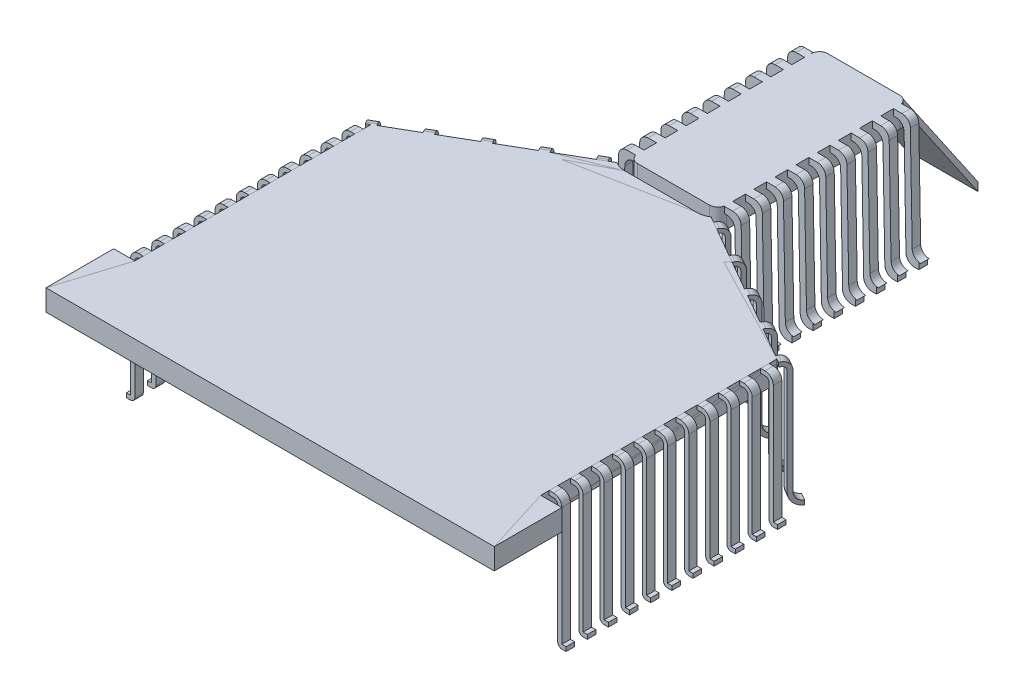
SolidWorks part; units mm, degrees
material "ABS"
ref_plane "Front Plane" through (0, 0, 0) normal (0, 0, 1) x (1, 0, 0)
ref_plane "Top Plane" through (0, 0, 0) normal (0, 1, 0) x (1, 0, 0)
ref_plane "Right Plane" through (0, 0, 0) normal (1, 0, 0) x (0, 0, -1)
sketch "Sketch1" plane through (0, 0, 0) normal (0, 1, 0) x (1, 0, 0)
  line L1 (-10.5, -22.5) -> (10.5, -22.5)
  line L2 (-10.5, -22.5) -> (-10.5, 22.5)
  line L3 (-10.5, 22.5) -> (10.5, 22.5)
  line L4 (10.5, -22.5) -> (10.5, 22.5)
  line L5 (-10.5, -22.5) -> (10.5, 22.5) construction
  line L6 (-10.5, 22.5) -> (10.5, -22.5) construction
  point P0 (0, 0)
  dimension "D1" = 21
  dimension "D2" = 45
extrude "Boss-Extrude1" add sketch "Sketch1" along normal blind 5
fillet "Fillet1" radius 2 4 edges at (-10.5, 2.5, -22.5) (-10.5, 2.5, 22.5) (10.5, 2.5, -22.5) (10.5, 2.5, 22.5)
sketch "Sketch2" plane through (0, 0, 0) normal (0, 0, 1) x (1, 0, 0)
  line L0 (10.5, 3.5) -> (11.0265, 3.5)
  line L1 (10.5, 5) -> (10.5, 0) construction
  line L2 (13.0262, 1.5357) -> (13.4649, -23.0357)
  line L3 (15.4646, -25) -> (16.5, -25)
  line L4 (-8.5, 5) -> (8.5, 5) construction
  line L5 (10.5, 5) -> (12.5, 5)
  line L6 (14.4997, 3.0357) -> (14.9384, -21.5357)
  line L7 (16.9381, -23.5) -> (16.5, -23.5)
  line L8 (10.5, 5) -> (10.5, 3.5)
  line L9 (16.5, -23.5) -> (16.5, -25)
  line L10 (14.4646, 5) -> (14.9735, -23.5) construction
  line L11 (14.9735, -23.5) -> (16.5, -23.5) construction
  line L12 (12.9912, 3.5) -> (13.5, -25) construction
  line L13 (13.5, -25) -> (16.5, -25) construction
  line L14 (10.5, 5) -> (14.4646, 5) construction
  line L15 (10.5, 3.5) -> (12.9912, 3.5) construction
  arc A0 (14.9384, -21.5357) -> (16.9381, -23.5) centre (16.9381, -21.5) ccw
  arc A1 (13.4649, -23.0357) -> (15.4646, -25) centre (15.4646, -23) ccw
  arc A2 (12.5, 5) -> (14.4997, 3.0357) centre (12.5, 3) cw
  arc A3 (11.0265, 3.5) -> (13.0262, 1.5357) centre (11.0265, 1.5) cw
  point P18 (13.5, -25)
  dimension "D2" = 3
  dimension "D7" = 2
  dimension "D1" = 2
  dimension "D3" = 3
  dimension "D4" = 30
  dimension "D5" = 1.5
  dimension "D6" = 1.5
extrude "Boss-Extrude2" add sketch "Sketch2" along normal mid plane 2
pattern_linear "LPattern1" count 5 spacing 5 along (0, 0, -1) count 5 spacing 5 along (0, 0, 1) of "Boss-Extrude2"
mirror "Mirror1" about plane through (0, 0, 0) normal (1, 0, 0) of "Boss-Extrude2", "LPattern1"
sketch "Sketch3" plane through (0, 0, 0) normal (1, 0, 0) x (0, 0, -1)
  line L0 (22.5, 5) -> (41, -22)
  line L2 (21, -21.5357) -> (21, 3.0357) construction
  dimension "D1" = 20
  dimension "D2" = 3
sketch "Sketch4" plane through (0, 0, -22.5) normal (0, 0, -1) x (-1, 0, 0)
  line L0 (8.5, 0) -> (8.5, 5) construction
  line L1 (-8.5, 5) -> (8.5, 5)
  line L2 (-8.5, 5) -> (-8.5, 3)
  line L3 (-8.5, 3) -> (8.5, 3)
  line L4 (8.5, 5) -> (8.5, 3)
  line L5 (-8.5, 5) -> (8.5, 3) construction
  line L6 (-8.5, 3) -> (8.5, 5) construction
  point P4 (0, 4)
  dimension "D1" = 2
sweep "Sweep1" add profiles "Sketch4" path "Sketch3"
sketch "Sketch5" plane through (0, 5, 0) normal (0, 1, 0) x (1, 0, 0)
  line L0 (-10.4616, -20.8899) -> (-51, -44.2948)
  line L1 (-51, -44.2948) -> (-51, -98.8899)
  line L2 (-51, -98.8899) -> (-56, -98.8899)
  line L3 (-56, -98.8899) -> (-56, -120.8899)
  line L4 (-56, -120.8899) -> (56, -120.8899)
  line L5 (0, 28.031) -> (0, -37.9663) construction
  line L6 (56, -98.8899) -> (56, -120.8899)
  line L7 (51, -98.8899) -> (56, -98.8899)
  line L8 (51, -44.2948) -> (51, -98.8899)
  line L9 (10.4616, -20.8899) -> (51, -44.2948)
  line L10 (-8.5, -22.5) -> (8.5, -22.5) construction
  line L11 (-8.5, -22.5) -> (8.5, -22.5)
  line L12 (-11.1404, -24.7459) -> (-48, -46.0268)
  line L13 (-48, -46.0268) -> (-48, -101.8899)
  line L14 (-48, -101.8899) -> (-53, -101.8899)
  line L15 (-53, -101.8899) -> (-53, -117.8899)
  line L16 (-53, -117.8899) -> (53, -117.8899)
  line L17 (53, -101.8899) -> (53, -117.8899)
  line L18 (48, -101.8899) -> (53, -101.8899)
  line L19 (48, -46.0268) -> (48, -101.8899)
  line L20 (11.1404, -24.7459) -> (48, -46.0268)
  line L21 (-8.5, -25.5) -> (8.5, -25.5)
  arc A0 (8.5, -22.5) -> (10.5, -20.5) centre (8.5, -20.5) ccw construction
  arc A1 (-10.5, -20.5) -> (-8.5, -22.5) centre (-8.5, -20.5) ccw construction
  arc A2 (8.5, -22.5) -> (10.4616, -20.8899) centre (8.5, -20.5) ccw
  arc A3 (-10.4616, -20.8899) -> (-8.5, -22.5) centre (-8.5, -20.5) ccw
  arc A4 (8.5, -25.5) -> (11.1404, -24.7459) centre (8.5, -20.5) ccw
  arc A5 (-11.1404, -24.7459) -> (-8.5, -25.5) centre (-8.5, -20.5) ccw
  point P11 (0, -120.8899)
  dimension "D1" = 120
  dimension "D2" = 22
  dimension "D3" = 5
  dimension "D4" = 56
  dimension "D5" = 51
  dimension "D6" = 100
  dimension "D7" = 3
extrude "Boss-Extrude3" [suppressed] add sketch "Sketch5" against normal blind 25
extrude "Boss-Extrude4" add sketch "Sketch5<2>" against normal blind 5 contours A5 L12 L13 L14 L15 L16 L17 L18 L19 L20 A4 L21 region at (0, 5, 75.8778)
sketch "Sketch5<2>" plane through (0, 5, 0) normal (0, 1, 0) x (1, 0, 0) same geometry as "Sketch5"
sketch "Sketch6" [suppressed] plane through (56, 0, 0) normal (1, 0, 0) x (0, 0, -1)
  line L0 (-104.8899, -2) -> (-114.8899, -2)
  line L1 (-114.8899, -2) -> (-114.8899, -13)
  line L2 (-114.8899, -13) -> (-104.8899, -13)
  line L3 (-104.8899, -13) -> (-104.8899, -2)
  line L12 (-120.8899, -20) -> (-120.8899, 5) construction
  line L13 (-120.8899, -20) -> (-98.8899, -20) construction
  line L14 (-120.8899, 5) -> (-98.8899, 5) construction
  line L15 (-98.8899, -20) -> (-98.8899, 5) construction
  dimension "D3" = 7
  dimension "D1" = 6
  dimension "D2" = 7
  dimension "D4" = 6
extrude "Cut-Extrude1" [suppressed] cut sketch "Sketch6" against normal through all both and the other way through all contours L2 L3 L0 L1
ref_plane "Plane1" through (55.9302, 0, 32.2913) normal (-0.866, 0, -0.5) x (0, 1, 0)
sketch "Sketch8" plane through (55.9302, 0, 32.2913) normal (-0.866, 0, -0.5) x (0, 1, 0)
  line L0 (5, -15.8604) -> (5, -15.3604)
  line L1 (3, -13.3604) -> (-22, -13.3604)
  line L2 (-24, -11.3604) -> (-25, -11.3604)
  line L4 (4, -15.8604) -> (4, -15.3604)
  line L5 (3, -14.3604) -> (-22, -14.3604)
  line L8 (5, -15.8604) -> (4, -15.8604)
  line L11 (-24, -10.3604) -> (-10.5, -10.3604) construction
  line L12 (-24, -11.3604) -> (-24, -10.3604) construction
  line L13 (-25, -9.3604) -> (-10.5, -9.3604) construction
  line L14 (-25, -11.3604) -> (-25, -9.3604) construction
  arc A0 (-22, -13.3604) -> (-24, -11.3604) centre (-22, -11.3604) cw
  arc A1 (5, -15.3604) -> (3, -13.3604) centre (3, -15.3604) ccw
  arc A2 (4, -15.3604) -> (3, -14.3604) centre (3, -15.3604) ccw
  arc A3 (-22, -14.3604) -> (-25, -11.3604) centre (-22, -11.3604) cw
  point P8 (-8.5, -13.3604)
  point P11 (5, -13.3604)
  dimension "D5" = 2
  dimension "D1" = 2.5
  dimension "D2" = 30
  dimension "D6" = 1
extrude "Boss-Extrude5" add sketch "Sketch8" along normal mid plane 2
pattern_linear "LPattern2" count 5 spacing 10 along (-0.866, 0, -0.5) of "Boss-Extrude5"
ref_plane "Plane2" through (0, 0, 101.8899) normal (0, 0, -1) x (0, 1, 0)
sketch "Sketch9" plane through (0, 0, 101.8899) normal (0, 0, -1) x (0, 1, 0)
  line L0 (4, 48) -> (4, 49)
  line L1 (3, 50) -> (-25, 50)
  line L2 (-26, 51) -> (-26, 52)
  line L3 (5, 48) -> (5, 49)
  line L4 (3, 51) -> (-25, 51)
  line L5 (-25, 51) -> (-25, 52)
  line L6 (-25, 52) -> (-26, 52)
  line L7 (5, 48) -> (4, 48)
  arc A0 (-25, 50) -> (-26, 51) centre (-25, 51) cw
  arc A1 (4, 49) -> (3, 50) centre (3, 49) ccw
  arc A2 (5, 49) -> (3, 51) centre (3, 49) ccw
  arc A3 (-25, 51) -> (-25, 51) centre (-25, 51) cw
  point P2 (0, 0)
  point P5 (0, 0)
  point P6 (5, 48)
  point P10 (-26, 50)
  point P13 (4, 50)
  dimension "D4" = 1
  dimension "D1" = 2
  dimension "D2" = 2
  dimension "D3" = 30
  dimension "D5" = 1
extrude "Boss-Extrude7" add sketch "Sketch9" along normal blind 2 from offset 2 separate body
pattern_linear "LPattern3" count 11 spacing 5 along (0, 0, -1) of "Boss-Extrude7"
mirror "Mirror6" about plane through (0, 0, 0) normal (1, 0, 0) of bodies 111 112 113 114 115 116 117 118 119 120 121 110
